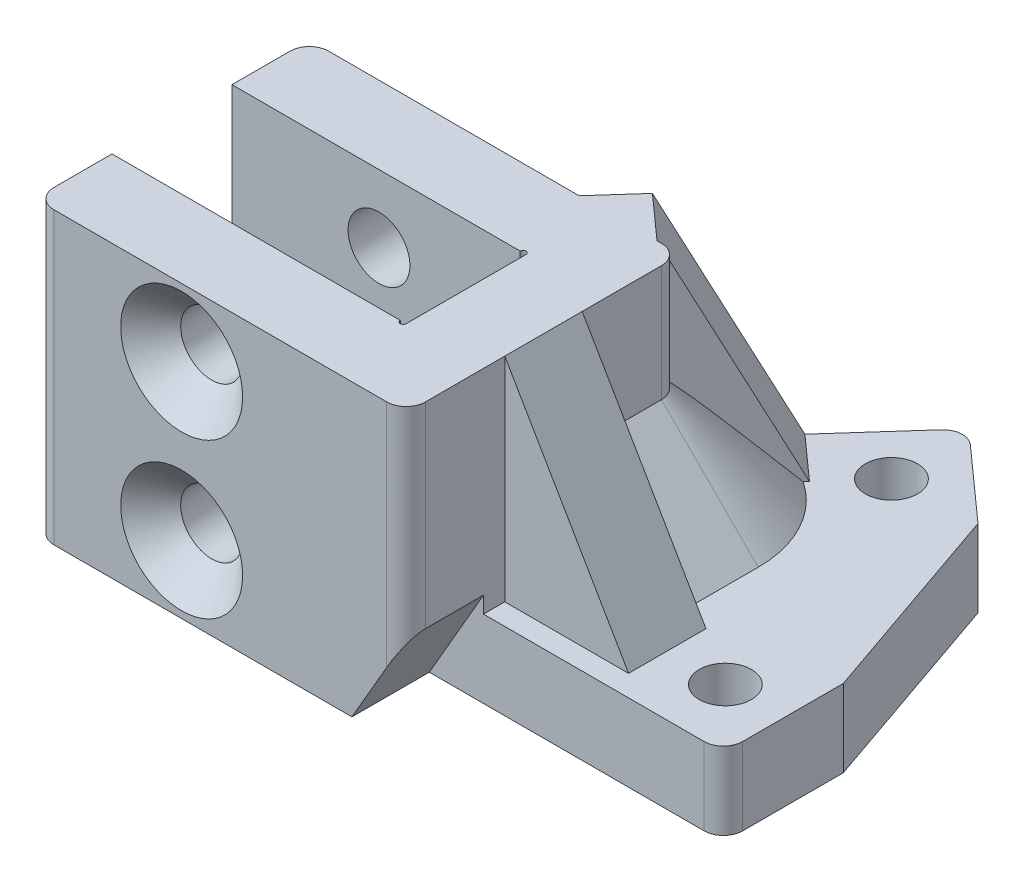
SolidWorks part; units mm, degrees
material "PLA"
ref_plane "前视基准面" through (0, 0, 0) normal (0, 0, 1) x (1, 0, 0)
ref_plane "上视基准面" through (0, 0, 0) normal (0, 1, 0) x (1, 0, 0)
ref_plane "右视基准面" through (0, 0, 0) normal (1, 0, 0) x (0, 0, -1)
sketch "草图1" plane through (0, 0, 0) normal (0, 1, 0) x (1, 0, 0)
  line L0 (-16.0869, 13.4985) -> (-18.086, 15.7354) construction
  line L1 (7.6, -3.1) -> (-7.6, -3.1) construction
  line L2 (7.6, -3.1) -> (7.6, 3.1)
  line L3 (7.6, 3.1) -> (-7.6, 3.1)
  line L4 (-7.6, -3.1) -> (-7.6, 3.1)
  line L5 (7.6, -3.1) -> (-7.6, 3.1) construction
  line L6 (7.6, 3.1) -> (-7.6, -3.1) construction
  line L7 (0, 0) -> (0, 11.678) construction
  line L8 (-6.3452, 7.1) -> (-15.8491, 17.7345)
  line L9 (-15.8491, 17.7345) -> (-20.3229, 13.7363)
  line L10 (-20.3229, 13.7363) -> (-11.6, 3.9758)
  line L11 (-11.6, 3.9758) -> (-11.6, 3.1)
  line L12 (-11.6, 3.1) -> (-24, 3.1)
  line L13 (-24, 3.1) -> (-24, -3.1)
  line L19 (-21, 0) -> (-8.6, 0) construction
  line L22 (6.3452, 7.1) -> (15.8491, 17.7345)
  line L23 (15.8491, 17.7345) -> (20.3229, 13.7363)
  line L24 (20.3229, 13.7363) -> (11.6, 3.9758)
  line L25 (11.6, 3.9758) -> (11.6, 3.1)
  line L26 (11.6, 3.1) -> (24, 3.1)
  line L30 (24, 3.1) -> (24, -3.1)
  line L31 (-6.3452, 7.1) -> (6.3452, 7.1)
  line L34 (-24, -3.1) -> (-7.6, -3.1)
  line L35 (24, -3.1) -> (7.6, -3.1)
  line L36 (0, 0) -> (-16.0869, 13.4985) construction
  circle A0 centre (0, 0) radius 21 construction
  circle A1 centre (-21, 0) radius 1.35
  circle A2 centre (-16.0869, 13.4985) radius 1.35
  circle A4 centre (16.0869, 13.4985) radius 1.35
  circle A5 centre (21, 0) radius 1.35
  dimension "D1" = 42
  dimension "D4" = 2.7
  dimension "D2" = 15.2
  dimension "D3" = 6.2
  dimension "D5" = 40
  dimension "D7" = 6
  dimension "D8" = 3
  dimension "D9" = 3
  dimension "D13" = 4
  dimension "D15" = 4
extrude "凸台-拉伸1" add sketch "草图1" along normal blind 4
sketch "草图3" plane through (0, 4, 0) normal (0, 1, 0) x (1, 0, 0)
  line L0 (0, 0) -> (0, 13.1344) construction
  line L2 (-6.3452, 7.1) -> (6.3452, 7.1)
  line L3 (6.3452, 7.1) -> (11.851, 13.2607)
  line L4 (15.8491, 17.7345) -> (6.3452, 7.1) construction
  line L5 (11.851, 13.2607) -> (14.0879, 11.2617)
  line L6 (14.0879, 11.2617) -> (10.3686, 7.1)
  line L7 (-7.6, 3.1) -> (7.6, 3.1) construction
  line L8 (-14.0879, 11.2617) -> (-10.3686, 7.1)
  line L9 (-11.851, 13.2607) -> (-14.0879, 11.2617)
  line L10 (-6.3452, 7.1) -> (-11.851, 13.2607)
  line L11 (-7.6, 3.1) -> (7.6, 3.1)
  line L12 (-11.6, -0.1) -> (-18, -0.1)
  line L13 (-7.6, -3.1) -> (-7.6, 3.1) construction
  line L15 (24, 0) -> (18.8885, 0) construction
  line L18 (-24, -3.1) -> (-7.6, -3.1) construction
  line L19 (-7.6, -3.1) -> (-18, -3.1)
  line L20 (-18, -3.1) -> (-18, -0.1)
  line L23 (11.6, 2) -> (18, 2)
  line L24 (18, -2) -> (18, 2)
  line L25 (-7.6, 3.1) -> (-7.6, -3.1)
  line L27 (-10.3686, 7.1) -> (-11.6, 7.1)
  line L28 (-11.6, 7.1) -> (-11.6, -0.1)
  line L29 (7.6, -2) -> (18, -2)
  line L30 (11.6, 7.1) -> (11.6, 2)
  line L31 (10.3686, 7.1) -> (11.6, 7.1)
  line L32 (7.6, 3.1) -> (7.6, -2)
  line L33 (24, -3.1) -> (24, 3.1) construction
  circle A0 centre (16.0869, 13.4985) radius 1.35 construction
  circle A1 centre (-21, 0) radius 1.35 construction
  circle A2 centre (21, 0) radius 1.35 construction
  dimension "D3" = 3
  dimension "D7" = 3
  dimension "D1" = 3
  dimension "D2" = 3
  dimension "D4" = 4
  dimension "D5" = 4
  dimension "D6" = 4
extrude "凸台-拉伸2" add sketch "草图3" along normal blind 11
sketch "草图4" plane through (0, 0, 3.1) normal (0, 0, 1) x (1, 0, 0)
  line L0 (-11.6, 15) -> (-11.6, 4) construction
  line L1 (-11.6, 15) -> (-11.6, 4) construction
  line L2 (-11.6, 15) -> (-18, 4)
  line L3 (-18, 4) -> (-18, 15)
  line L4 (-18, 15) -> (-11.6, 15)
  line L5 (0, 0) -> (0, 12.485) construction
  line L6 (-7.6, 0) -> (7.6, 0) construction
  line L7 (18, 4) -> (18, 15)
  line L8 (11.6, 15) -> (18, 4)
  line L9 (18, 15) -> (11.6, 15)
extrude "切除-拉伸1" cut sketch "草图4" against normal blind 10
sketch "草图5" plane through (0, 0, 0) normal (-0.7456, 0, -0.6664) x (-0.6664, 0, 0.7456)
  line L0 (-12.2032, 15) -> (-17.7846, 4)
  line L1 (-17.7846, 4) -> (-17.7846, 15)
  line L2 (-17.7846, 15) -> (-12.2032, 15)
  line L4 (-12.2032, 15) -> (-17.7846, 15) construction
  line L5 (-12.2032, 15) -> (-17.7846, 15) construction
extrude "切除-拉伸2" cut sketch "草图5" against normal blind 3
mirror "镜向2" about plane through (0, 0, 0) normal (1, 0, 0) of "切除-拉伸2"
sketch "草图6" plane through (0, 0, -7.1) normal (0, 0, -1) x (-1, 0, 0)
  line L0 (0, 0) -> (0, 13.5753) construction
  line L1 (-6.3452, 0) -> (6.3452, 0) construction
  line L2 (-6.3452, 7.5) -> (1.4774, 7.5) construction
  line L3 (-6.3452, 15) -> (-6.3452, 0) construction
  circle A0 centre (0, 11.5) radius 1.6
  circle A1 centre (0, 3.5) radius 1.6
  dimension "D2" = 3.2
  dimension "D1" = 8
extrude "切除-拉伸3" cut sketch "草图6" against normal through all
sketch "草图7" plane through (0, 15, 0) normal (0, 1, 0) x (1, 0, 0)
  line L0 (-7.6, 3.1) -> (7.6, 3.1) construction
  circle A0 centre (7.45, 3.1) radius 0.15
  circle A1 centre (-7.45, 3.1) radius 0.15 construction
  dimension "D1" = 0.3
extrude "切除-拉伸4" cut sketch "草图7" against normal through all
sketch "草图8" plane through (0, 15, 0) normal (0, 1, 0) x (1, 0, 0)
  line L0 (-7.6, 3.1) -> (-7.6, 24.7345) construction
  line L1 (-7.6, 3.1) -> (7.3, 3.1) construction
  line L2 (-7.6, 24.7345) -> (-31, 24.7345)
  line L3 (-31, 24.7345) -> (-31, -10.1)
  line L4 (-7.6, 3.1) -> (-7.6, -10.1)
  line L5 (-7.6, -10.1) -> (-31, -10.1)
  line L6 (-18, -3.1) -> (-11.6, -3.1) construction
  line L7 (-24, 3.1) -> (-24, -3.1) construction
  line L8 (-7.6, -3.1) -> (-7.6, 3.1) construction
  line L9 (-7.6, 7.1) -> (-2.6, 7.1)
  line L10 (6.3452, 7.1) -> (-6.3452, 7.1) construction
  line L11 (-2.6, 7.1) -> (-2.6, 24.7345)
  line L12 (-2.6, 24.7345) -> (-7.6, 24.7345)
  line L13 (-7.6, 7.1) -> (-7.6, 3.1)
  dimension "D1" = 5
  dimension "D2" = 7
  dimension "D3" = 7
  dimension "D4" = 7
extrude "切除-拉伸5" cut sketch "草图8" against normal through all
mirror "镜向3" about plane through (0, 0, 0) normal (0, 0, 1) of bodies 121
sketch "草图9" plane through (0, 15, 0) normal (0, 1, 0) x (1, 0, 0)
  line L4 (6.3452, -7.1) -> (11.6, -7.1)
  line L5 (6.3452, -7.1) -> (-7.6, -7.1) construction
  line L6 (21.3452, -3.9758) -> (21.3452, -18.9758)
  line L7 (21.3452, -18.9758) -> (6.3452, -18.9758)
  line L8 (6.3452, -18.9758) -> (6.3452, -7.1)
  line L9 (-7.6, -3.1) -> (-7.6, -7.1) construction
  line L10 (11.6, -3.9758) -> (11.6, -7.1)
  line L11 (11.6, -3.9758) -> (21.3452, -3.9758)
  dimension "D1" = 15
  dimension "D2" = 13.9452
extrude "切除-拉伸6" cut sketch "草图9" against normal through all
hole_wizard "M3 锥坑高头螺钉的锥形沉头孔3" positions "3D草图2" profile "草图11" countersink size "M3" standard "ISO" end condition through all
sketch3d "3D草图2"
  line L0 (0, 11.5, 3.1) -> (0, 11.5, 7.1) construction
  line L1 (0, 3.5, 3.1) -> (0, 3.5, 7.1) construction
  point P0 (0, 11.5, 7.1)
  point P4 (0, 3.5, 7.1)
sketch "草图11" plane through (0, 11.5, 7.1) normal (1, 0, 0) x (0, -1, 0)
  line L0 (0, 0) -> (0, 24.8345)
  line L1 (0, 24.8345) -> (1.6, 24.8345)
  line L2 (1.6, 24.8345) -> (1.6, 1.55)
  line L3 (1.6, 1.55) -> (3.15, 0)
  line L5 (3.15, 0) -> (0, 0)
  line L6 (-1.6, 1.55) -> (-3.15, 0) construction
  line L11 (0, -6.35) -> (0, 107.95) construction
  dimension "通孔孔直径" = 3.2
  dimension "通孔孔深度" = 24.8345
  dimension "近端锥形沉头孔直径" = 6.3
  dimension "近端锥形沉头孔角度" = 90
sketch "草图12" plane through (0, 4, 0) normal (0, 1, 0) x (1, 0, 0)
  line L0 (11.6, 3.9758) -> (20.3229, 13.7363)
  line L1 (20.3229, 13.7363) -> (24, 3.1)
  line L2 (24, 3.1) -> (11.6, 3.1)
  line L3 (11.6, 3.1) -> (11.6, 3.9758)
extrude "凸台-拉伸3" add sketch "草图12" against normal up to surface (4 mm away) up to face at (8.0187, 0, -2.0851)
fillet "圆角1" radius 1 6 edges at (11.6, 9.5, -7.1) (24, 2, 3.1) (15.8491, 2, -17.7345) (-7.6, 7.5, -7.1) (-7.6, 7.5, 7.1) (11.6, 7.5, 7.1)
chamfer "倒角1" distance 5 angle 45 3 edges at (10.4843, 4, -7.1) (11.3071, 4, -6.8071) (11.6, 4, -4.05)
sketch "草图13" plane through (0, 0, 7.1) normal (0, 0, 1) x (1, 0, 0)
  line L0 (11.6, 4.8497) -> (8.8, 0)
  line L1 (11.6, 4) -> (11.6, 0) construction
  line L2 (10.6, 0) -> (-6.6, 0) construction
  line L3 (8.8, 0) -> (11.6, 0)
  line L4 (11.6, 0) -> (11.6, 4.8497)
  dimension "D1" = 2.8
  dimension "D2" = 30
extrude "切除-拉伸7" cut sketch "草图13" along direction (0, 0, -1) on the side against the normal up to surface (4 mm away) up to face at (17.3, 2, 3.1)
